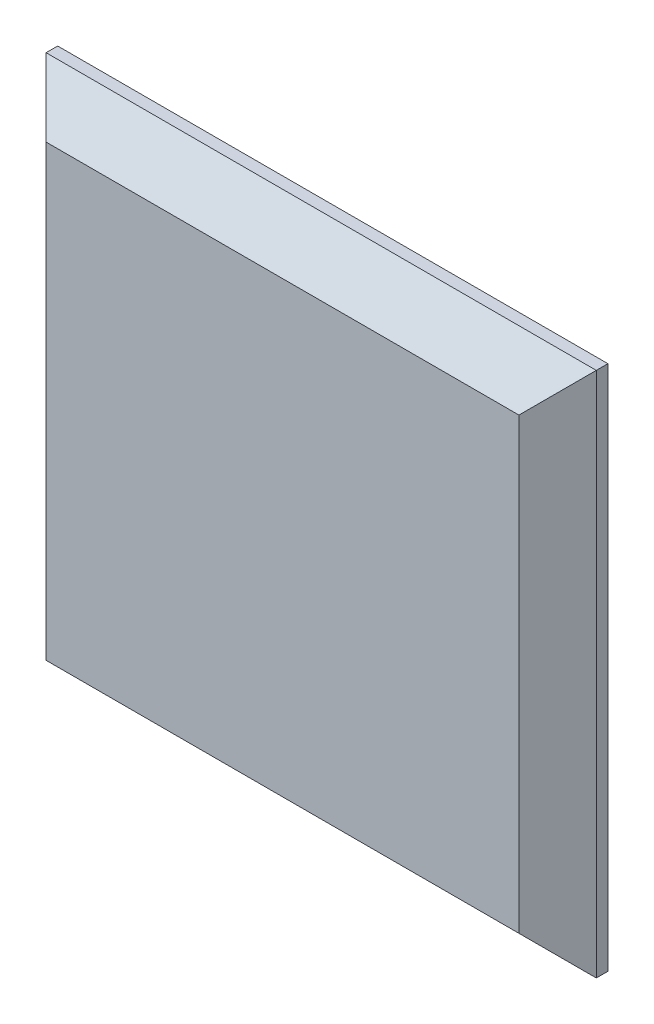
SolidWorks part; units mm, degrees
ref_plane "Front Plane" through (0, 0, 0) normal (0, 0, 1) x (1, 0, 0)
ref_plane "Top Plane" through (0, 0, 0) normal (0, 1, 0) x (1, 0, 0)
ref_plane "Right Plane" through (0, 0, 0) normal (1, 0, 0) x (0, 0, -1)
sketch "Sketch1" plane through (0, 0, 0) normal (0, 0, 1) x (1, 0, 0)
  line L1 (-137.2, 73) -> (-137.2, 85)
  line L8 (0, 0) -> (0, 136)
  line L9 (0, 136) -> (-191, 136)
  line L10 (-191, 136) -> (-191, 0)
  line L11 (-191, 0) -> (0, 0)
  line L12 (-142.2, 136) -> (-142.2, 0)
  line L13 (-137.2, 5) -> (-137.2, 131)
  line L14 (-137.2, 5) -> (-5, 5)
  line L15 (-5, 5) -> (-5, 131)
  line L16 (-5, 131) -> (-137.2, 131)
  circle A0 centre (-5, 131) radius 3
  circle A1 centre (-5, 5) radius 3
  circle A2 centre (-137.2, 131) radius 3
  circle A3 centre (-137.2, 5) radius 3
  dimension "D2" = 6
  dimension "D3" = 6
  dimension "D4" = 6
  dimension "D5" = 6
  dimension "D6" = 5
extrude "Boss-Extrude1" add sketch "Sketch1" along normal blind 10 contours L9 L12 L11 L8 A3 L13 L1 A2 L16 A0 L15 A1 L14 | L13 A3 L14 | L14 A3 L13 | L16 A2 L13 | L13 A2 L16 | L15 A0 L16 | L16 A0 L15 | L14 A1 L15 | L15 A1 L14 region at (-135.9268, 6.2732, 0) region at (-137.6244, 4.5756, 0) region at (-137.6244, 131.4244, 0) region at (-135.9268, 129.7268, 0) region at (-6.2732, 6.2732, 0) region at (-4.5756, 4.5756, 0) region at (-4.5756, 131.4244, 0) region at (-6.2732, 129.7268, 0) region at (-71.1, 1.9677, 0)
sketch "Sketch2" plane through (0, 0, 10) normal (0, 0, 1) x (1, 0, 0)
  line L0 (0, 136) -> (-142.2, 136) construction
  line L1 (0, 0) -> (0, 136) construction
  line L2 (-142.2, 0) -> (0, 0) construction
  line L3 (-142.2, 136) -> (-142.2, 0) construction
  line L4 (-142.2, 136) -> (-142.2, 0)
  line L5 (-142.2, 0) -> (0, 0)
  line L6 (0, 0) -> (0, 136)
  line L7 (0, 136) -> (-142.2, 136)
extrude "Boss-Extrude2" add sketch "Sketch2" along normal blind 3
chamfer "Chamfer1" distance 10 angle 45 4 edges at (0, 68, 13) (-71.1, 136, 13) (-142.2, 68, 13) (-71.1, 0, 13)
chamfer "Chamfer2" distance 8 angle 45 4 edges at (-71.1, 131, 10) (-5, 68, 10) (-71.1, 5, 10) (-137.2, 68, 10)
sketch "Sketch3" plane through (0, 0, 0) normal (0, 0, -1) x (-1, 0, 0)
  circle A0 centre (5, 5) radius 1.55 construction
  circle A1 centre (5, 131) radius 1.55 construction
  circle A2 centre (137.2, 5) radius 1.55 construction
  circle A3 centre (137.2, 131) radius 1.55 construction
  circle A4 centre (5, 5) radius 1.55
  circle A5 centre (5, 131) radius 1.55
  circle A6 centre (137.2, 5) radius 1.55
  circle A7 centre (137.2, 131) radius 1.55
extrude "Cut-Extrude1" cut sketch "Sketch3" against normal blind 2
